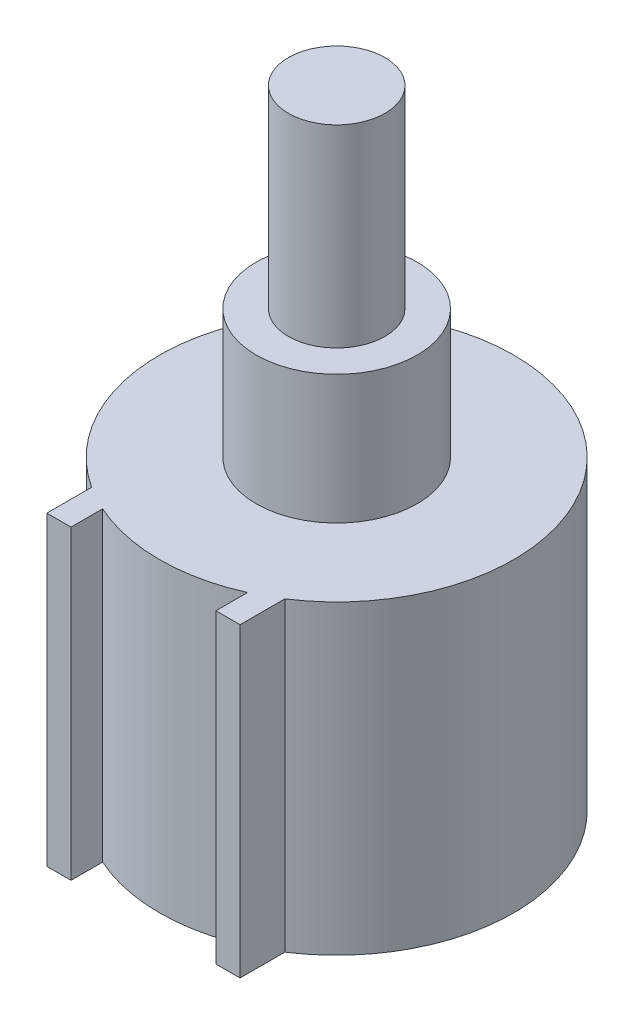
SolidWorks part; units mm, degrees
ref_plane "Front Plane" through (0, 0, 0) normal (0, 0, 1) x (1, 0, 0)
ref_plane "Top Plane" through (0, 0, 0) normal (0, 1, 0) x (1, 0, 0)
ref_plane "Right Plane" through (0, 0, 0) normal (1, 0, 0) x (0, 0, -1)
sketch "Sketch1" plane through (0, 0, 0) normal (0, 1, 0) x (1, 0, 0)
  line L1 (-6, -12) -> (-4.5, -12)
  line L2 (-6, -12) -> (-6, -9.2195)
  line L4 (-4.5, -12) -> (-4.5, -10.0374)
  line L5 (4.5, -12) -> (6, -12)
  line L6 (4.5, -12) -> (4.5, -10.0374)
  line L8 (6, -12) -> (6, -9.2195)
  arc A0 (-4.5, -10.0374) -> (4.5, -10.0374) centre (0, 0) ccw
  arc A1 (6, -9.2195) -> (-6, -9.2195) centre (0, 0) ccw
  point P11 (0, 0)
  point P12 (0, 0)
  dimension "D1" = 22
  dimension "D2" = 12
  dimension "D3" = 9
  dimension "D4" = 4.5
  dimension "D5" = 1.5
extrude "Boss-Extrude1" add sketch "Sketch1" along normal blind 19
sketch "Sketch2" plane through (0, 19, 0) normal (0, 1, 0) x (1, 0, 0)
  circle A0 centre (0, 0) radius 5
  dimension "D1" = 10
extrude "Boss-Extrude2" add sketch "Sketch2" along normal blind 8
sketch "Sketch3" plane through (0, 27, 0) normal (0, 1, 0) x (1, 0, 0)
  circle A0 centre (0, 0) radius 3
  dimension "D1" = 6
extrude "Boss-Extrude3" add sketch "Sketch3" along normal blind 12
